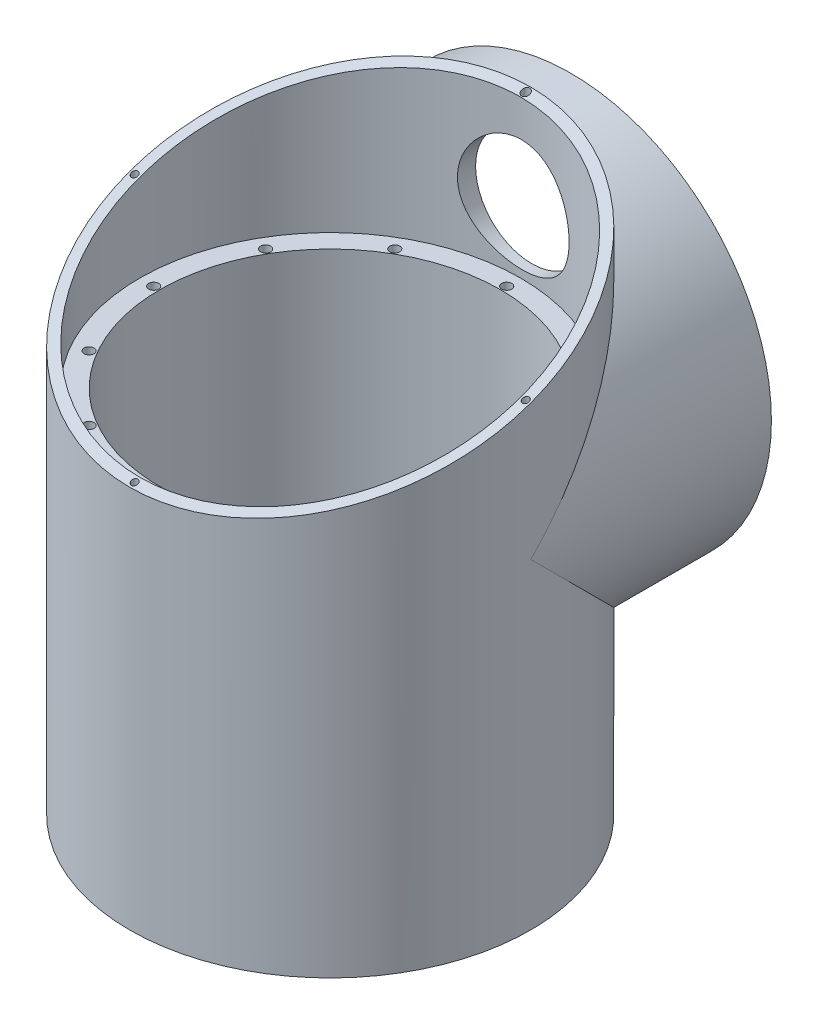
SolidWorks part; units mm, degrees
ref_plane "前视基准面" through (0, 0, 0) normal (0, 0, 1) x (1, 0, 0)
ref_plane "上视基准面" through (0, 0, 0) normal (0, 1, 0) x (1, 0, 0)
ref_plane "右视基准面" through (0, 0, 0) normal (1, 0, 0) x (0, 0, -1)
sketch "草图1" plane through (0, 0, 0) normal (0, 0, 1) x (1, 0, 0)
  circle A0 centre (0, 0) radius 50
  dimension "D1" = 100
extrude "凸台-拉伸1" add sketch "草图1" along normal blind 60
sketch "草图2" plane through (0, 0, 0) normal (0, 1, 0) x (1, 0, 0)
  line L0 (-50, -60) -> (50, -60) construction
  circle A0 centre (0, -60) radius 50
extrude "凸台-拉伸2" add sketch "草图2" along normal blind 52 and the other way blind 80 contours A0
sketch "草图3" plane through (0, -80, 0) normal (0, -1, 0) x (1, 0, 0)
  circle A0 centre (0, 60) radius 25
  dimension "D1" = 50
extrude "切除-拉伸1" cut sketch "草图3" against normal through all contours A0
sketch "草图4" plane through (0, -80, 0) normal (0, -1, 0) x (1, 0, 0)
  circle A0 centre (0, 60) radius 42
  dimension "D1" = 84
extrude "切除-拉伸2" cut sketch "草图4" against normal blind 23
hole_wizard "M3 螺纹孔1" positions "草图6" profile "草图5" tap size "M3" standard "GB"
sketch "草图6" plane through (0, -57, 0) normal (0, -1, 0) x (-1, 0, 0)
  line L0 (0, -60) -> (0, -106.9825) construction
  circle A0 centre (0, -60) radius 37 construction
  point P0 (0, -97)
  dimension "D1" = 74
sketch "草图5" plane through (0, -57, 97) normal (1, 0, 0) x (0, 0, -1)
  line L0 (0, 0) -> (0, 8.2511)
  line L1 (0, 8.2511) -> (1.25, 7.5)
  line L2 (1.25, 7.5) -> (1.25, 0)
  line L5 (1.25, 0) -> (0, 0)
  line L10 (0, 8.2511) -> (-1.25, 7.5) construction
  line L11 (0, -6.35) -> (0, 107.95) construction
  dimension "螺纹孔钻头直径" = 2.5
  dimension "螺纹孔钻头深度" = 7.5
  dimension "导头角度" = 118
cosmetic thread "孔螺蚊线1" parameters "D1"=6, "D2"=3
ref_axis "基准轴1" through (0, -80, 60) along (0, 1, 0)
pattern_circular "阵列(圆周)1" count 12 over 360 about axis through (0, -80, 60) along (0, 1, 0) of "M3 螺纹孔1"
sketch "草图7" plane through (0, 52, 0) normal (0, 1, 0) x (1, 0, 0)
  circle A0 centre (0, -60) radius 42.49
  dimension "D1" = 84.98
extrude "切除-拉伸3" cut sketch "草图7" against normal offset from surface (97 mm away) 12 contours A0 up to face at (-18.5, -57, 90.7929)
sketch "草图8" plane through (0, 52, 0) normal (0, 1, 0) x (1, 0, 0)
  circle A0 centre (0, -60) radius 47.5
  dimension "D1" = 95
extrude "切除-拉伸4" cut sketch "草图8" against normal offset from surface (40 mm away) 57 up to face at (0, -45, 17.51)
hole_wizard "M3 螺纹孔2" positions "草图10" profile "草图9" tap size "M3" standard "GB"
sketch "草图10" plane through (0, 12, 0) normal (0, 1, 0) x (1, 0, 0)
  line L0 (0, -60) -> (0, 3.704) construction
  circle A0 centre (0, -60) radius 44 construction
  point P0 (0, -16)
  dimension "D1" = 88
sketch "草图9" plane through (0, 12, 16) normal (1, 0, 0) x (0, 0, 1)
  line L0 (0, 0) -> (0, 8.2511)
  line L1 (0, 8.2511) -> (1.25, 7.5)
  line L2 (1.25, 7.5) -> (1.25, 0)
  line L5 (1.25, 0) -> (0, 0)
  line L10 (0, 8.2511) -> (-1.25, 7.5) construction
  line L11 (0, -6.35) -> (0, 107.95) construction
  dimension "螺纹孔钻头直径" = 2.5
  dimension "螺纹孔钻头深度" = 7.5
  dimension "导头角度" = 118
cosmetic thread "孔螺蚊线4" parameters "D1"=6, "D2"=3
pattern_circular "阵列(圆周)2" count 12 over 360 about axis through (0, -80, 60) along (0, 1, 0) of "M3 螺纹孔2"
sketch "草图11" plane through (0, 0, 0) normal (1, 0, 0) x (0, 0, -1)
  line L0 (-10, 52) -> (-110, 52)
  line L1 (-110, 52) -> (-110, 15.603)
  line L2 (-110, 52) -> (-110, -80) construction
  line L3 (-110, 15.603) -> (-10, 52)
  dimension "D1" = 20
extrude "切除-拉伸5" cut sketch "草图11" against normal through all and the other way through all contours L0 L1 L3
ref_plane "基准面1" through (0, 52, 0) normal (0, -1, 0) x (-1, 0, 0)
sketch "草图12" plane through (0, 52, 0) normal (0, -1, 0) x (-1, 0, 0)
  line L0 (0, -60) -> (0, 8.1254) construction
  circle A0 centre (0, -60) radius 48.75 construction
  circle A1 centre (0, -11.25) radius 1
  dimension "D1" = 97.5
  dimension "D2" = 2
extrude "切除-拉伸8" cut sketch "草图12" along normal blind 4 contours A1
sketch "草图14" plane through (0, 52, 0) normal (0, -1, 0) x (-1, 0, 0)
  line L0 (0, -60) -> (0, -113.5669) construction
  circle A0 centre (0, -60) radius 48.75 construction
  circle A1 centre (0, -108.75) radius 0.8
  dimension "D1" = 97.5
  dimension "D2" = 1.6
extrude "切除-拉伸9" cut sketch "草图14" along normal blind 40
sketch "草图15" plane through (0, 52, 0) normal (0, -1, 0) x (-1, 0, 0)
  line L0 (61.919, -60) -> (-62.4871, -60) construction
  circle A0 centre (0, -60) radius 48.75 construction
  circle A1 centre (48.75, -60) radius 0.8
  circle A2 centre (-48.75, -60) radius 0.8
  dimension "D1" = 97.5
  dimension "D2" = 1.6
  dimension "D3" = 1.6
extrude "切除-拉伸10" cut sketch "草图15" along normal blind 25
hole_wizard "M3 螺纹孔3" positions "草图17" profile "草图16" tap size "M3" standard "GB"
sketch "草图17" plane through (0, 0, 0) normal (0, 0, -1) x (-1, 0, 0)
  line L0 (0, 0) -> (0, 57.6253) construction
  circle A0 centre (0, 0) radius 46 construction
  point P0 (0, 46)
  dimension "D1" = 92
sketch "草图16" plane through (0, 46, 0) normal (1, 0, 0) x (0, 1, 0)
  line L0 (0, 0) -> (0, 8.2511)
  line L1 (0, 8.2511) -> (1.25, 7.5)
  line L2 (1.25, 7.5) -> (1.25, 0)
  line L5 (1.25, 0) -> (0, 0)
  line L10 (0, 8.2511) -> (-1.25, 7.5) construction
  line L11 (0, -6.35) -> (0, 107.95) construction
  dimension "螺纹孔钻头直径" = 2.5
  dimension "螺纹孔钻头深度" = 7.5
  dimension "导头角度" = 118
cosmetic thread "孔螺蚊线3" parameters "D1"=6, "D2"=3
ref_axis "基准轴2" through (0, 0, 60) along (0, 0, -1)
pattern_circular "阵列(圆周)3" count 12 over 360 about axis through (0, 0, 60) along (0, 0, -1) of "M3 螺纹孔3"
sketch "草图18" plane through (0, 0, 0) normal (0, 0, -1) x (-1, 0, 0)
  circle A0 centre (0, 0) radius 42.5
  dimension "D1" = 85
extrude "切除-拉伸11" cut sketch "草图18" against normal blind 10
sketch "草图19" plane through (0, 0, 10) normal (0, 0, -1) x (-1, 0, 0)
  line L0 (0, 0) -> (0, 55.3301) construction
  line L1 (-25.7354, 28) -> (25.2357, 28) construction
  circle A0 centre (-0.2499, 28) radius 14
  dimension "D2" = 28
  dimension "D1" = 28
extrude "切除-拉伸12" cut sketch "草图19" against normal blind 10
